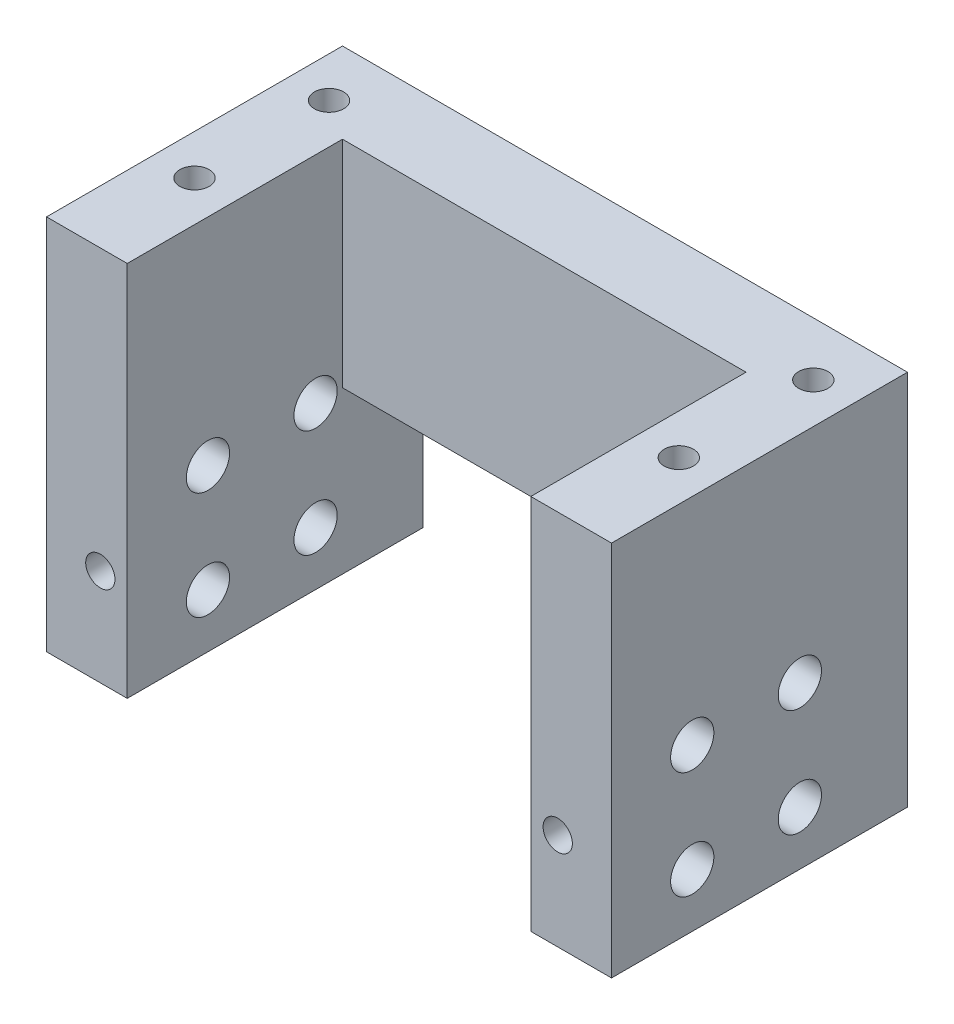
SolidWorks part; units mm, degrees
ref_plane "Front Plane" through (0, 0, 0) normal (0, 0, 1) x (1, 0, 0)
ref_plane "Top Plane" through (0, 0, 0) normal (0, 1, 0) x (1, 0, 0)
ref_plane "Right Plane" through (0, 0, 0) normal (1, 0, 0) x (0, 0, -1)
sketch "Sketch1" plane through (0, 0, 0) normal (0, 1, 0) x (1, 0, 0)
  line L1 (-33.3375, 17.4625) -> (33.3375, 17.4625)
  line L2 (-33.3375, 17.4625) -> (-33.3375, -17.4625)
  line L3 (-33.3375, -17.4625) -> (33.3375, -17.4625)
  line L4 (33.3375, 17.4625) -> (33.3375, -17.4625)
  dimension "D1" = 33.3375
  dimension "D2" = 33.3375
  dimension "D3" = 17.4625
  dimension "D4" = 17.4625
extrude "Boss-Extrude1" add sketch "Sketch1" along normal mid plane 76.2
sketch "Sketch2" plane through (0, 38.1, 0) normal (0, 1, 0) x (1, 0, 0)
  line L0 (-33.3375, -17.4625) -> (33.3375, -17.4625) construction
  line L1 (-23.8125, -17.4625) -> (23.8125, -17.4625)
  line L2 (-23.8125, -17.4625) -> (-23.8125, 7.9375)
  line L3 (-23.8125, 7.9375) -> (23.8125, 7.9375)
  line L4 (23.8125, -17.4625) -> (23.8125, 7.9375)
  line L5 (-33.3375, 17.4625) -> (-33.3375, -17.4625) construction
  line L6 (33.3375, -17.4625) -> (33.3375, 17.4625) construction
  line L7 (33.3375, 17.4625) -> (-33.3375, 17.4625) construction
  dimension "D1" = 9.525
  dimension "D2" = 9.525
  dimension "D3" = 9.525
extrude "Cut-Extrude1" cut sketch "Sketch2" against normal through all
sketch "Sketch3" plane through (33.3375, 0, 0) normal (1, 0, 0) x (0, 0, -1)
  line L0 (-17.4625, 38.1) -> (17.4625, 38.1) construction
  line L1 (-17.4625, -38.1) -> (17.4625, -38.1)
  line L2 (-17.4625, -38.1) -> (-17.4625, -6.35)
  line L3 (-17.4625, -6.35) -> (17.4625, -6.35)
  line L4 (17.4625, -38.1) -> (17.4625, -6.35)
  line L5 (17.4625, 38.1) -> (17.4625, -38.1) construction
  dimension "D1" = 44.45
  dimension "D2" = 0
extrude "Cut-Extrude2" cut sketch "Sketch3" against normal through all
sketch "Sketch4" plane through (0, 0, -17.4625) normal (0, 0, -1) x (-1, 0, 0)
  line L1 (23.8125, -6.35) -> (23.8125, 38.1) construction
  line L2 (23.8125, 12.7) -> (-23.8125, 12.7)
  line L3 (23.8125, 12.7) -> (23.8125, -25.4)
  line L4 (23.8125, -25.4) -> (-23.8125, -25.4)
  line L7 (-23.8125, 12.7) -> (-23.8125, -25.4)
  line L8 (-23.8125, -6.35) -> (-23.8125, 38.1) construction
  line L9 (-23.8125, 38.1) -> (23.8125, 38.1) construction
  dimension "D1" = 25.4
  dimension "D2" = 38.1
extrude "Cut-Extrude3" cut sketch "Sketch4" against normal through all
hole_wizard "1/4-20 Tapped Hole1" positions "Sketch6" profile "Sketch5" tap size "1/4-20" standard "ANSI Inch" end condition up to next
sketch "Sketch6" plane through (33.3375, 0, 0) normal (1, 0, 0) x (0, 0, -1)
  line L0 (-17.4625, 38.1) -> (-17.4625, -6.35) construction
  line L2 (17.4625, 38.1) -> (17.4625, -6.35) construction
  line L3 (17.4625, -6.35) -> (-17.4625, -6.35) construction
  point P0 (-7.9375, 0)
  point P2 (4.7625, 0)
  dimension "D1" = 9.525
  dimension "D2" = 12.7
  dimension "D3" = 6.35
  dimension "D4" = 12.7
sketch "Sketch5" plane through (33.3375, 0, 7.9375) normal (0, 1, 0) x (0, 0, -1)
  line L0 (0, 0) -> (0, 9.526)
  line L1 (0, 9.526) -> (2.5527, 9.526)
  line L2 (2.5527, 9.526) -> (2.5527, 0)
  line L5 (2.5527, 0) -> (0, 0)
  line L11 (0, -6.35) -> (0, 107.95) construction
  dimension "Thru Tap Drill Dia." = 5.1054
  dimension "Thru Tap Drill Depth" = 9.526
cosmetic thread "Hole Thread1" parameters "D2"=6.35
cosmetic thread "Hole Thread2" parameters "D2"=6.35
hole_wizard "#8-32 Tapped Hole1" positions "Sketch8" profile "Sketch7" tap size "#8-32" standard "ANSI Inch"
sketch "Sketch8" plane through (0, 0, 17.4625) normal (0, 0, 1) x (1, 0, 0)
  line L0 (23.8125, -6.35) -> (23.8125, 38.1) construction
  line L1 (23.8125, -6.35) -> (33.3375, -6.35) construction
  point P0 (26.9875, 5.08)
  dimension "D1" = 3.175
  dimension "D2" = 11.43
sketch "Sketch7" plane through (26.9875, 5.08, 17.4625) normal (1, 0, 0) x (0, -1, 0)
  line L0 (0, 0) -> (0, 13.4838)
  line L1 (0, 13.4838) -> (1.7272, 12.446)
  line L2 (1.7272, 12.446) -> (1.7272, 0)
  line L5 (1.7272, 0) -> (0, 0)
  line L10 (0, 13.4838) -> (-1.7272, 12.446) construction
  line L11 (0, -6.35) -> (0, 107.95) construction
  dimension "Tap Drill Dia." = 3.4544
  dimension "Tap Drill Depth" = 12.446
  dimension "Drill Angle" = 118
cosmetic thread "Hole Thread3" parameters "D1"=8.382, "D2"=4.1656
hole_wizard "#8-32 Tapped Hole2" positions "Sketch10" profile "Sketch9" tap size "#8-32" standard "ANSI Inch"
sketch "Sketch10" plane through (0, 38.1, 0) normal (0, 1, 0) x (1, 0, 0)
  line L0 (33.3375, -17.4625) -> (33.3375, 17.4625) construction
  line L1 (23.8125, -17.4625) -> (33.3375, -17.4625) construction
  line L2 (33.3375, 17.4625) -> (-33.3375, 17.4625) construction
  point P0 (28.575, -4.7625)
  point P2 (28.575, 11.1125)
  dimension "D1" = 4.7625
  dimension "D2" = 12.7
  dimension "D3" = 6.35
sketch "Sketch9" plane through (28.575, 38.1, 4.7625) normal (1, 0, 0) x (0, 0, 1)
  line L0 (0, 0) -> (0, 13.4838)
  line L1 (0, 13.4838) -> (1.7272, 12.446)
  line L2 (1.7272, 12.446) -> (1.7272, 0)
  line L5 (1.7272, 0) -> (0, 0)
  line L10 (0, 13.4838) -> (-1.7272, 12.446) construction
  line L11 (0, -6.35) -> (0, 107.95) construction
  dimension "Tap Drill Dia." = 3.4544
  dimension "Tap Drill Depth" = 12.446
  dimension "Drill Angle" = 118
cosmetic thread "Hole Thread4" parameters "D1"=8.382, "D2"=4.1656
cosmetic thread "Hole Thread5" parameters "D1"=8.382, "D2"=4.1656
pattern_linear "LPattern1" count 2 spacing 12.7 along (0, 1, 0) of "1/4-20 Tapped Hole1"
mirror "Mirror1" about plane through (0, 0, 0) normal (1, 0, 0) of "LPattern1", "#8-32 Tapped Hole1", "#8-32 Tapped Hole2"
